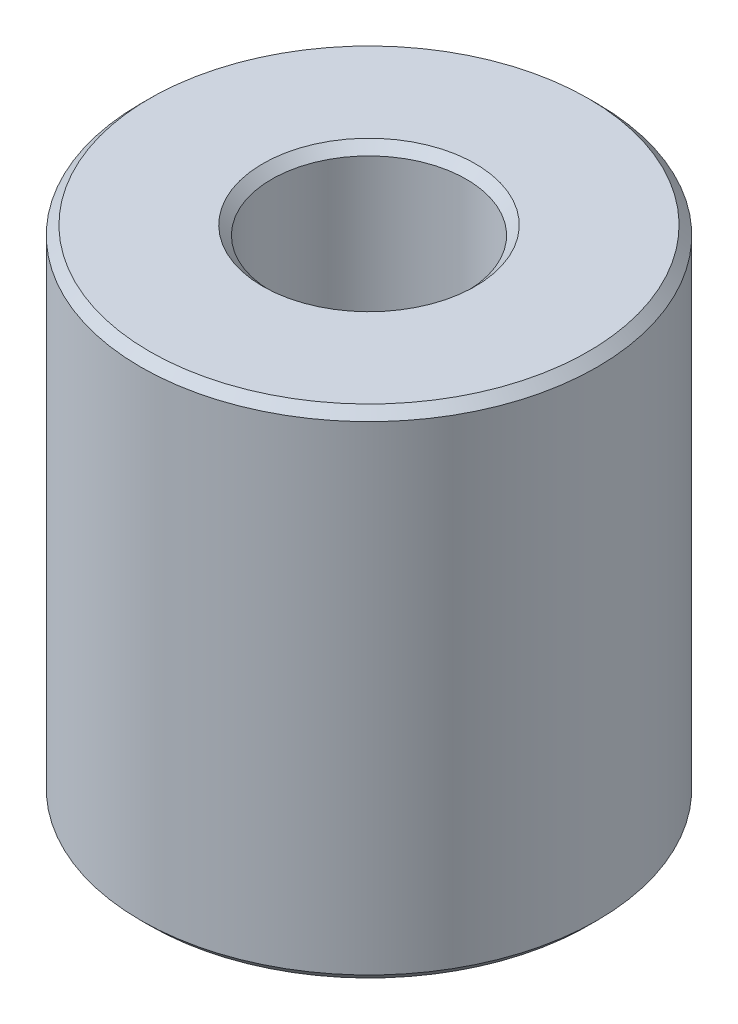
SolidWorks part; units mm, degrees
ref_plane "Front Plane" through (0, 0, 0) normal (0, 0, 1) x (1, 0, 0)
ref_plane "Top Plane" through (0, 0, 0) normal (0, 1, 0) x (1, 0, 0)
ref_plane "Right Plane" through (0, 0, 0) normal (1, 0, 0) x (0, 0, -1)
sketch "Sketch1" plane through (0, 0, 0) normal (0, 1, 0) x (1, 0, 0)
  circle A0 centre (0, 0) radius 27.5
  dimension "SLEEVE_OD" = 55
extrude "Boss-Extrude1" add sketch "Sketch1" along normal blind 59.8982
sketch "Sketch2" plane through (0, 0, 0) normal (0, 1, 0) x (1, 0, 0)
  circle A0 centre (0, 0) radius 11.7267
  dimension "BORE_D" = 23.4534
extrude "Cut-Extrude1" cut sketch "Sketch2" along normal through all
chamfer "Chamfer1" distance 1.0791 angle 45 4 edges at (0, 59.8982, 11.7267) (0, 0, 11.7267) (0, 0, 27.5) (0, 59.8982, 27.5)
